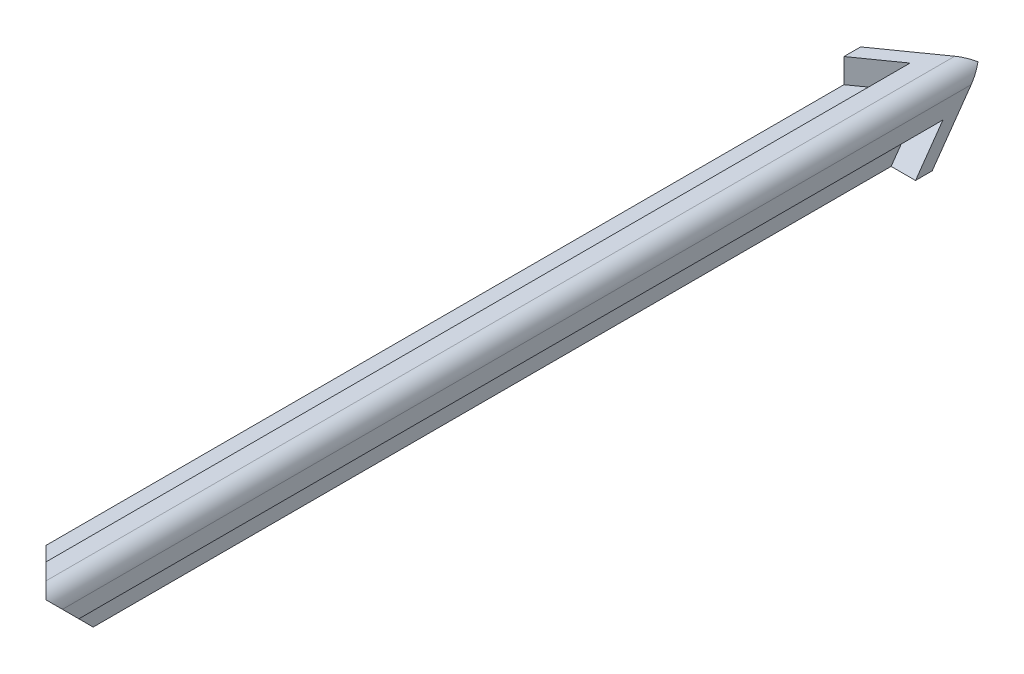
SolidWorks part; units mm, degrees
note: '?' marks a value the reader was unsure of.
ref_plane "Front Plane" through (0, 0, 0) normal (0, 0, 1) x (1, 0, 0)
ref_plane "Top Plane" through (0, 0, 0) normal (0, 1, 0) x (1, 0, 0)
ref_plane "Right Plane" through (0, 0, 0) normal (1, 0, 0) x (0, 0, -1)
ref_axis "Axis1" through (0, 0, -88.99) along (0, 0, 1)?
sketch "Sketch16" plane through (0, 0, 0) normal (0, 1, 0) x (1, 0, 0)
  line L0 (0, -127) -> (0, 127) construction
  point P2 (0, 0)
  dimension "D1" = 254
sketch "Sketch2" plane through (0, 0, 0) normal (0, 0, 1) x (1, 0, 0)
  line L0 (-7.3025, -1.5) -> (-2.54, -1.5) construction
  line L1 (-7.3025, -1.5) -> (-7.3025, 1.5) construction
  line L2 (-2.54, -1.5) -> (-2.54, 1.5) construction
  line L3 (-7.3025, 1.5) -> (-2.54, 1.5) construction
  line L4 (-2.54, 0) -> (0, 0) construction
  line L5 (0, 0) -> (0, -2.54) construction
  line L6 (-1.5, -2.54) -> (1.5, -2.54) construction
  line L7 (-1.5, -2.54) -> (-1.5, -7.3025) construction
  line L8 (1.5, -2.54) -> (1.5, -7.3025) construction
  line L9 (-1.5, -7.3025) -> (1.5, -7.3025) construction
  point P7 (0, -2.54)
  point P16 (1.5, 1.5)
  dimension "D1" = 3
  dimension "D2" = 4.7625
  dimension "D3" = 2.54
  dimension "D4" = 90
ref_plane "Plane1" through (0, 0, 0) normal (-1, 0, 0) x (0, -1, 0)
sketch "Sketch7" plane through (0, 0, 0) normal (0, 0, 1) x (1, 0, 0)
  line L0 (-7.3025, -1.5) -> (-2.54, -1.5)
  line L1 (-7.3025, -1.5) -> (-7.3025, -3.6212)
  line L2 (-2.54, -1.5) -> (-2.54, -3.6212)
  line L3 (-7.3025, -3.6212) -> (-2.54, -3.6212)
  dimension "D1" = 2.1212
extrude "Boss-Extrude2" add sketch "Sketch7" along normal mid plane 260.35 separate body
sketch "Sketch8" plane through (0, 0, 0) normal (0, 0, 1) x (1, 0, 0)
  line L0 (-1.5, -2.54) -> (-1.5, -7.3025)
  line L1 (-1.5, -2.54) -> (-3.6212, -2.54)
  line L2 (-1.5, -7.3025) -> (-3.6212, -7.3025)
  line L3 (-3.6212, -2.54) -> (-3.6212, -7.3025)
  line L4 (-2.54, -3.6212) -> (-2.54, -1.5) construction
extrude "Boss-Extrude3" add sketch "Sketch8" along normal mid plane 260.35
sketch "Sketch11" plane through (0, 0, 0) normal (0, 0, 1) x (1, 0, 0)
  line L0 (-2.54, 1.5) -> (-2.54, -1.5)
  line L1 (-2.54, -1.5) -> (-7.3025, -1.5)
  line L2 (-7.3025, -1.5) -> (-7.3025, -3.6212)
  line L3 (-7.3025, -3.6212) -> (-5.8663, -3.6212)
  line L4 (-7.3025, -3.6212) -> (-3.6212, -3.6212) construction
  line L5 (-5.8663, -3.6212) -> (-3.6212, -5.8663)
  line L6 (-3.6212, -3.6212) -> (-3.6212, -7.3025) construction
  line L7 (-3.6212, -5.8663) -> (-3.6212, -7.3025)
  line L8 (-3.6212, -7.3025) -> (-1.5, -7.3025)
  line L9 (-1.5, -7.3025) -> (-1.5, -2.54)
  line L10 (-1.5, -2.54) -> (1.5, -2.54)
  line L13 (-2.54, 1.5) -> (-2.54, -2.54) construction
  line L14 (-2.54, -2.54) -> (1.5, -2.54) construction
  line L15 (1.5, -2.54) -> (1.5, -0.52)
  line L17 (-2.54, 1.5) -> (-0.52, 1.5)
  line L18 (-0.52, -0.52) -> (-0.52, 1.5) construction
  arc A0 (1.5, -0.52) -> (-0.52, 1.5) centre (-0.52, -0.52) ccw
  dimension "D1" = 3.175
extrude "Boss-Extrude4" add sketch "Sketch11" along normal mid plane 260.35
sketch "Sketch14" plane through (0, 0, 0) normal (0, 1, 0) x (1, 0, 0)
  line L0 (-7.3025, -104.0263) -> (-7.3025, -149.9737)
  line L1 (-7.3025, -130.175) -> (-7.3025, 130.175) construction
  line L2 (-7.3025, -149.9737) -> (7.3025, -149.9737)
  line L4 (7.3025, -149.9737) -> (-7.3025, -104.0263)
  line L5 (0, 88.99) -> (0, -88.99) construction
  line L6 (0, -127) -> (0, 127) construction
  line L8 (-7.3025, 104.0263) -> (7.3025, 149.9737)
  line L9 (7.3025, 149.9737) -> (-7.3025, 149.9737)
  line L10 (-7.3025, 149.9737) -> (-7.3025, 104.0263)
  point P5 (0, -127)
  point P13 (0, 127)
  dimension "D2" = 17.634
  dimension "D1" = 17.634
extrude "Cut-Extrude4" [suppressed] cut sketch "Sketch14" against normal through all both and the other way through all
sketch "Sketch17" plane through (0, 0, 0) normal (-1, 0, 0) x (0, -1, 0)
  line L0 (7.3025, 144.6298) -> (7.3025, 109.3702)
  line L2 (7.3025, 109.3702) -> (-7.3025, 144.6298)
  line L3 (-7.3025, 144.6298) -> (7.3025, 144.6298)
  line L4 (7.3025, -109.3702) -> (-7.3025, -144.6298)
  line L5 (-7.3025, -144.6298) -> (7.3025, -144.6298)
  line L6 (7.3025, -144.6298) -> (7.3025, -109.3702)
  point P4 (0, 127)
  point P10 (0, -127)
  dimension "D1" = 22.5
  dimension "D2" = 22.5
  dimension "D3" = 7.3025
extrude "Cut-Extrude5" [suppressed] cut sketch "Sketch17" against normal through all both and the other way through all
ref_plane "Midplane" through (0, 0, 0) normal (-0.7071, 0.7071, 0) x (0.7071, 0.7071, 0)
sketch "Sketch18" plane through (0, 0, 113.7049) normal (-0.5774, -0.5774, -0.5774) x (-0.7071, 0.7071, 0)
  line L0 (0, 0) -> (63.5, 36.6617)
  line L1 (63.5, 36.6617) -> (0, -73.3235)
  line L2 (0, -73.3235) -> (0, 0) construction
  line L3 (63.5, 36.6617) -> (-63.5, 36.6617) construction
  line L4 (-63.5, 36.6617) -> (0, 0)
  line L5 (0, -73.3235) -> (-63.5, 36.6617)
  dimension "D1" = 127
extrude "Cut-Extrude6" cut sketch "Sketch18" against normal through all both and the other way through all
sketch "Sketch19" plane through (-66.6068, -160.803, 0) normal (0.7071, 0.7071, 0) x (0.7071, -0.7071, 0)
  line L0 (-66.6068, 0) -> (187.3932, -254)
  line L2 (187.3932, -254) -> (187.3932, 254)
  line L3 (187.3932, 254) -> (-320.6068, 254)
  line L4 (-320.6068, 254) -> (-320.6068, -254)
  line L6 (-320.6068, -254) -> (-66.6068, 0)
  line L7 (-66.6068, 254) -> (-66.6068, 0) construction
  line L8 (-66.6068, 0) -> (187.3932, 0) construction
  point P7 (-293.447, -225.3881)
  point P8 (188.1882, -254.7938)
  dimension "D1" = 90
  dimension "D2" = 508
extrude "Cut-Extrude7" cut sketch "Sketch19" against normal through all both and the other way through all
sketch "Sketch20" plane through (-2.54, 0, 0) normal (-1, 0, 0) x (0, 0, 1)
  line L0 (4.9069, 1.5) -> (4.9069, -1.5)
  line L1 (111.1649, -1.5) -> (0.7354, -1.5) construction
  line L2 (4.9069, -1.5) -> (0.7354, -1.5)
  line L3 (0.7354, -1.5) -> (2.8567, 1.5)
  line L4 (2.8567, 1.5) -> (4.9069, 1.5)
sweep "Sweep1" add profiles "Sketch20" path edge at (-4.9212, -1.5, 2.4192)
sketch "Sketch21" plane through (0, -2.54, 0) normal (0, -1, 0) x (1, 0, 0)
  line L0 (-1.5, 4.9069) -> (1.5, 4.9069)
  line L2 (1.5, 111.1649) -> (1.5, 2.8567) construction
  line L3 (1.5, 4.9069) -> (1.5, 2.8567)
  line L4 (1.5, 2.8567) -> (-1.5, 0.7354)
  line L5 (-1.5, 0.7354) -> (-1.5, 4.9069)
  line L6 (-1.5, 106.4024) -> (-1.5, 4.103) construction
  point P2 (-1.5, 5.0795)
  point P6 (-0.52, 5.6685)
sweep "Sweep2" add profiles "Sketch21" path edge at (-1.5, -4.9212, 2.4192)
equation "\"plate_thickness\"= 3mm"
equation "\"D1@Sketch2\"=\"plate_thickness\""
equation "\"joiner_lip_width\"= .1875"
equation "\"D2@Sketch2\"=\"joiner_lip_width\""
equation "\"face_gap\"=0.1"
equation "\"D3@Sketch2\"=\"face_gap\""
equation "\"inside_angle\"= 90"
equation "\"joiner_thickness\"= 0.0835128"
equation "\"edge_length\"= 10"
equation "\"Face1_TopLip\"= \"angle\" * 2"
equation "\"Face1_BottomLip\"= \"angle\" * 2"
equation "\"Face2_TopLip\"= 45deg"
equation "\"Face2_BottomLip\"= 45deg"
equation "\"D1@Sketch7\"=\"joiner_thickness\""
equation "\"D1@Boss-Extrude2\"=\"Extrude_to\""
equation "\"D1@Boss-Extrude3\"=\"Extrude_to\""
equation "\"D1@Boss-Extrude4\"=\"Extrude_to\""
equation "\"D4@Sketch2\"=\"inside_angle\""
equation "\"Extrude_to\"= \"edge_length\" + .25"
equation "\"D2@Sketch14\"=\"Face1_BottomLip\"/2"
equation "\"D1@Sketch16\"=\"edge_length\""
equation "\"D1@Sketch14\"=\"Face1_TopLip\"/2"
equation "\"D1@Sketch17\"=\"Face2_TopLip\"/2"
equation "\"D2@Sketch17\"=\"Face2_BottomLip\"/2"
equation "\"D3@Sketch17\"=\"joiner_lip_width\"+\"face_gap\""
equation "\"angle\"= atn ( 0.1 / ( ( 3.7085 - 3.0793 ) / 2 ) )"
equation "\"D2@Sketch5\"=\"Face2_TopLip\"/2"
equation "\"D1@Sketch5\"=\"Face2_BottomLip\"/2"
equation "\"D2@Sketch4\"=\"Face1_TopLip\"/2"
equation "\"D1@Sketch4\"=\"Face1_BottomLip\"/2"
equation "\"D1\" = \"edge_length\""
equation "\"D2@Sketch12\"=\"Face1_TopLip\"/2"
equation "\"D1@Sketch12\"=\"Face1_BottomLip\"/2"
